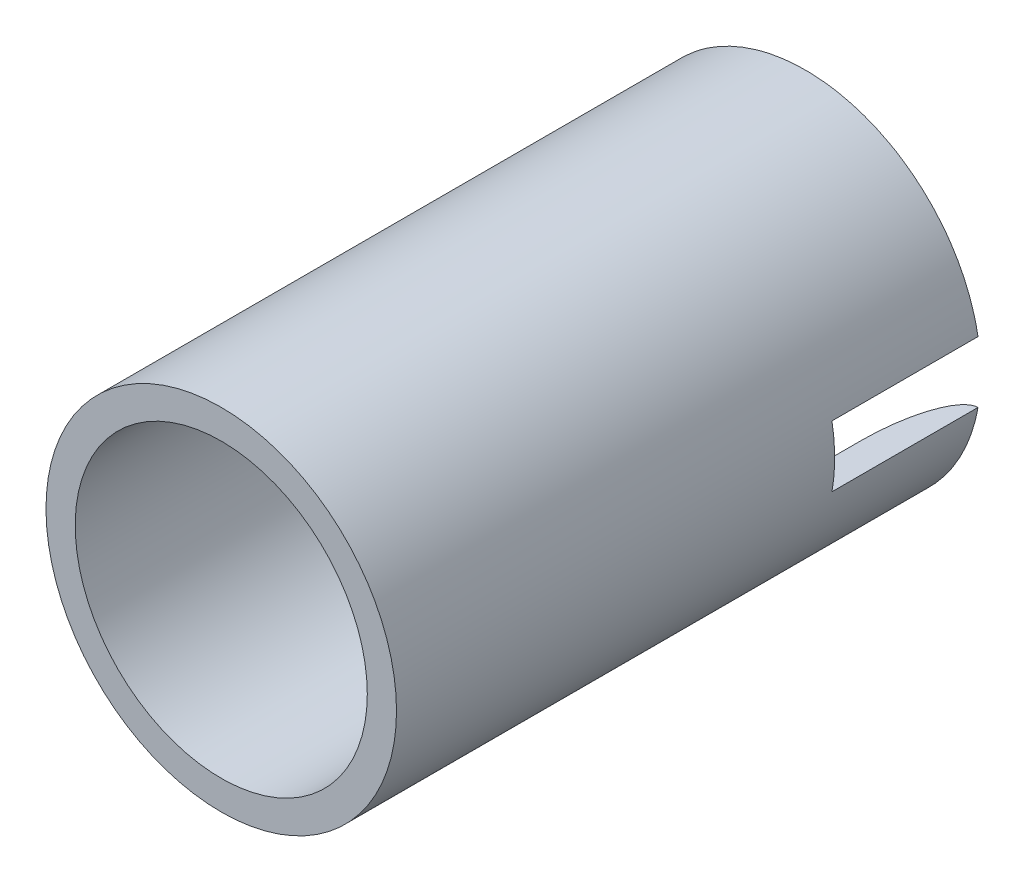
SolidWorks part; units mm, degrees
ref_plane "Front Plane" through (0, 0, 0) normal (0, 0, 1) x (1, 0, 0)
ref_plane "Top Plane" through (0, 0, 0) normal (0, 1, 0) x (1, 0, 0)
ref_plane "Right Plane" through (0, 0, 0) normal (1, 0, 0) x (0, 0, -1)
sketch "Sketch1" plane through (0, 0, 0) normal (0, 0, 1) x (1, 0, 0)
  circle A0 centre (0, 0) radius 5
  circle A1 centre (0, 0) radius 6
  dimension "D1" = 10
  dimension "D2" = 1
extrude "Boss-Extrude1" add sketch "Sketch1" along normal blind 20
sketch "Sketch2" plane through (0, 0, 0) normal (0, 0, -1) x (-1, 0, 0)
  line L1 (-8.9438, -1.05) -> (8.9438, -1.05)
  line L2 (-8.9438, -1.05) -> (-8.9438, 1.05)
  line L3 (-8.9438, 1.05) -> (8.9438, 1.05)
  line L4 (8.9438, -1.05) -> (8.9438, 1.05)
  line L5 (-8.9438, -1.05) -> (8.9438, 1.05) construction
  line L6 (-8.9438, 1.05) -> (8.9438, -1.05) construction
  point P0 (0, 0)
  dimension "D1" = 2.1
extrude "Cut-Extrude1" cut sketch "Sketch2" against normal blind 5
fillet "Fillet2" radius 3 2 edges at (0, -5, 0) (0, 5, 0) second distance 1 first distance on face at (0, 0, 2.5)
